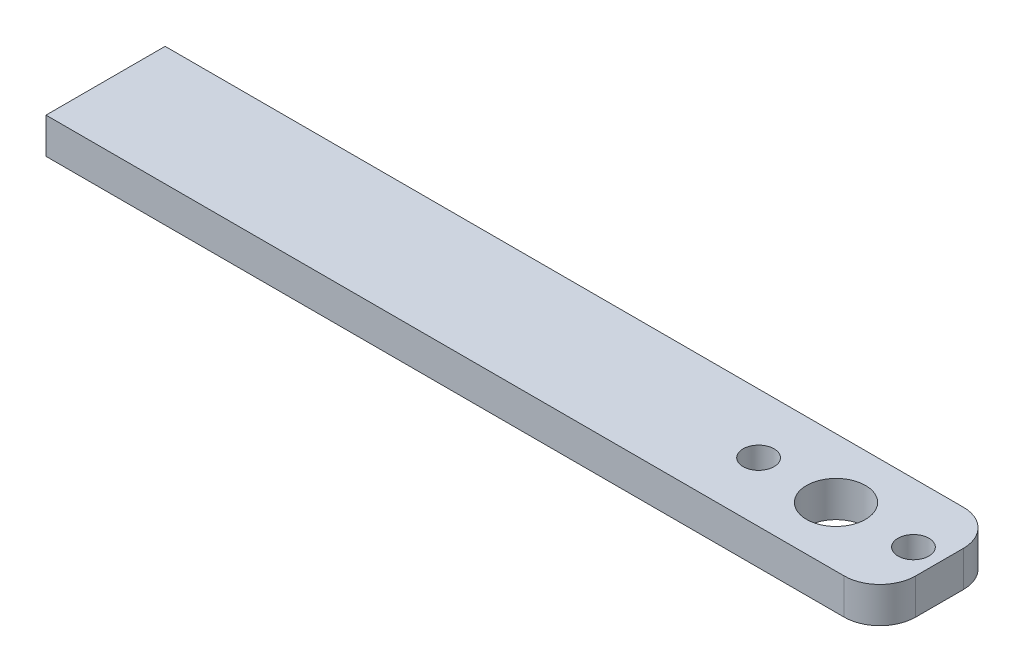
SolidWorks part; units mm, degrees
ref_plane "Front Plane" through (0, 0, 0) normal (0, 0, 1) x (1, 0, 0)
ref_plane "Top Plane" through (0, 0, 0) normal (0, 1, 0) x (1, 0, 0)
ref_plane "Right Plane" through (0, 0, 0) normal (1, 0, 0) x (0, 0, -1)
sketch "Sketch1" plane through (0, 0, 0) normal (0, 1, 0) x (1, 0, 0)
  line L1 (-35, 5) -> (35, 5)
  line L2 (-35, 5) -> (-35, -5)
  line L3 (-35, -5) -> (35, -5)
  line L4 (35, 5) -> (35, -5)
  line L5 (-35, 5) -> (35, -5) construction
  line L6 (-35, -5) -> (35, 5) construction
  point P0 (0, 0)
  dimension "D1" = 10
  dimension "D2" = 70
extrude "Boss-Extrude1" add sketch "Sketch1" along normal blind 3
sketch "Sketch2" plane through (0, 3, 0) normal (0, 1, 0) x (1, 0, 0)
  line L0 (26.3156, 5) -> (26.3156, -5) construction
  line L1 (-35, -5) -> (35, -5) construction
  circle A0 centre (26.3156, 0) radius 2.4729
  circle A1 centre (32.8156, 0) radius 1.3
  circle A3 centre (19.8156, 0) radius 1.3
  point P10 (26.3156, 0)
  point P11 (25.4084, -0.4685)
  point P12 (26.3156, 0)
  dimension "D1" = 2.6
  dimension "D2" = 6.5
extrude "Cut-Extrude1" cut sketch "Sketch2" against normal blind 3
fillet "Fillet1" radius 3 2 edges at (35, 1.5, 5) (35, 1.5, -5)
